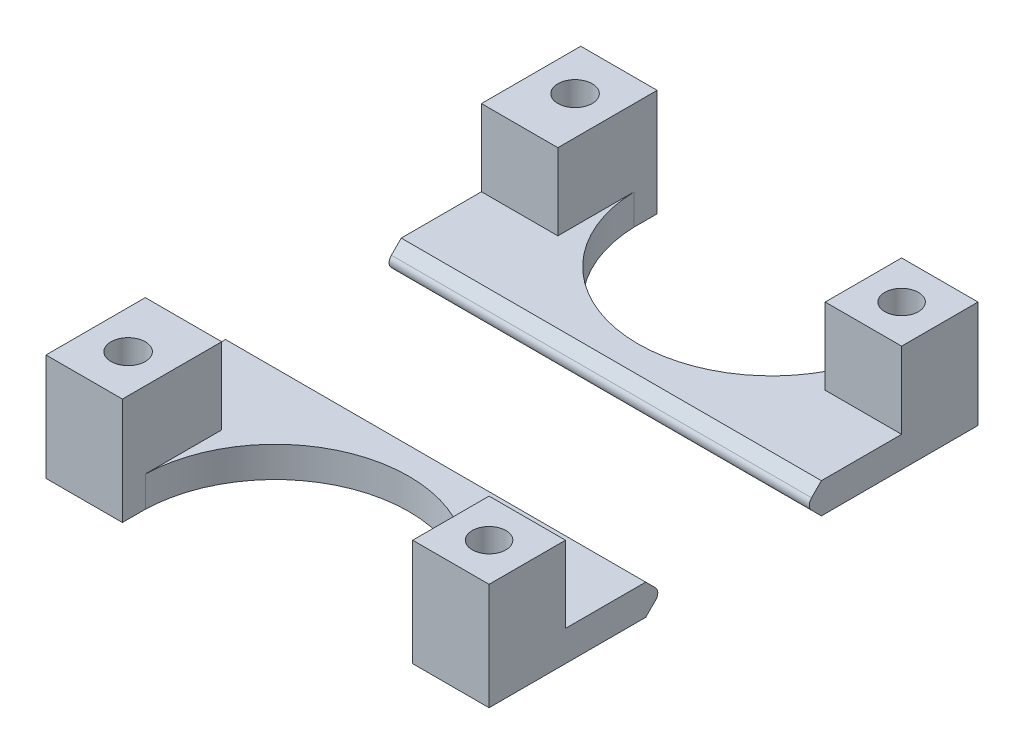
SolidWorks part; units mm, degrees
ref_plane "Front Plane" through (0, 0, 0) normal (0, 0, 1) x (1, 0, 0)
ref_plane "Top Plane" through (0, 0, 0) normal (0, 1, 0) x (1, 0, 0)
ref_plane "Right Plane" through (0, 0, 0) normal (1, 0, 0) x (0, 0, -1)
sketch "Sketch1" plane through (0, 0, 0) normal (0, 1, 0) x (1, 0, 0)
  line L0 (10, 10) -> (10, -10)
  line L2 (0, -20) -> (0, 20)
  line L4 (55, -20) -> (55, 20) construction
  line L5 (10, -10) -> (45, -10)
  line L6 (45, -10) -> (45, 10) construction
  line L7 (45, 10) -> (10, 10)
  line L8 (45, 10) -> (55, 10)
  line L11 (55, 10) -> (55, 20)
  line L13 (27.5, -20) -> (27.5, -10) construction
  line L14 (27.5, 10) -> (27.5, 20) construction
  line L16 (45, -10) -> (55, -10)
  line L17 (55, -20) -> (55, -10)
  line L18 (55, -20) -> (55, -32)
  line L19 (55, -32) -> (45, -32)
  line L20 (0, -32) -> (0, -35)
  line L21 (55, 20) -> (55, 32)
  line L22 (55, 32) -> (45, 32)
  line L23 (0, -35) -> (10, -35)
  line L24 (0, -20) -> (0, -32)
  line L26 (10, -35) -> (10, -32)
  line L27 (0, 20) -> (0, 32)
  line L29 (10, 32) -> (10, 35)
  line L30 (-55, 0) -> (55, 0) construction
  line L31 (0, 0) -> (55, 0) construction
  line L35 (10, 35) -> (0, 35)
  line L36 (0, 35) -> (0, 32)
  arc A26 (45, -32) -> (10, -32) centre (27.5, -32.5074) ccw
  arc A27 (45, 32) -> (10, 32) centre (27.5, 32.5074) cw
  circle A46 centre (50, 27) radius 2.2
  circle A47 centre (50, -27) radius 2.2
  circle A50 centre (5, 29.25) radius 2.2479
  circle A52 centre (5, -29.25) radius 2.2479
  point P30 (27.5, -15)
  point P35 (27.5, 15)
  point P36 (27.5, -10)
  point P39 (0, 0)
  dimension "D18" = 4.4
  dimension "D1" = 40
  dimension "D2" = 55
  dimension "D24" = 10
  dimension "D13" = 5
  dimension "D16" = 5
  dimension "D7" = 10
  dimension "D9" = 5
  dimension "D14" = 5
  dimension "D4" = 20
  dimension "D5" = 10
  dimension "D3" = 10
  dimension "D6" = 35
  dimension "D8" = 12
  dimension "D10" = 10
extrude "Extrude-Body" add sketch "Sketch1" along normal blind 4 contours L4 L2 A47 A46 L7 L6 L5 L0 | L19 L18 A47 | L22 L21 A46 | L27 | L24 region at (9.1098, 0, 0)
sketch "Sketch5" plane through (0, 4, 0) normal (0, 1, 0) x (1, 0, 0)
  line L9 (45, -22) -> (55, -22)
  line L21 (55, -22) -> (55, -32)
  line L23 (0, -35) -> (0, 35) construction
  line L36 (55, -32) -> (45, -32)
  line L37 (45, -32) -> (45, -22)
  line L38 (55, 22) -> (55, 32)
  line L39 (55, 32) -> (45, 32)
  line L41 (45, 32) -> (45, 22)
  line L42 (45, 22) -> (55, 22)
  line L43 (10, 22) -> (10, 35)
  line L45 (10, 35) -> (0, 35)
  line L46 (0, 35) -> (0, 22)
  line L47 (0, -35) -> (0, 35) construction
  line L48 (0, 22) -> (10, 22)
  line L49 (10, -22) -> (0, -22)
  line L50 (0, -22) -> (0, -35)
  line L52 (10, -35) -> (10, -22)
  line L55 (10, -35) -> (0, -35)
  circle A0 centre (50, 27) radius 2.2
  circle A3 centre (50, -27) radius 2.2
  circle A11 centre (50, 27) radius 2.2 construction
  circle A12 centre (50, -27) radius 2.2 construction
  circle A13 centre (5, -29.25) radius 2.2479 construction
  circle A14 centre (5, -29.25) radius 2.2479
  circle A15 centre (5, 29.25) radius 2.2479 construction
  circle A16 centre (5, 29.25) radius 2.2479
  dimension "D1" = 10
  dimension "D2" = 10
  dimension "D3" = 10
  dimension "D4" = 10
  dimension "D5" = 10
  dimension "D6" = 10
  dimension "D8" = 13
extrude "Extrude-Legs" add sketch "Sketch5" along normal blind 10
sketch "Sketch6" plane through (0, 4, 0) normal (0, 1, 0) x (1, 0, 0)
  line L0 (55, -10) -> (55, -22) construction
  line L1 (10, -10) -> (55, -10)
  line L2 (10, -10) -> (10, -9.5)
  line L3 (10, -9.5) -> (55, -9.5)
  line L4 (55, -10) -> (55, -9.5)
  line L5 (10, 10) -> (55, 10)
  line L6 (10, 10) -> (10, 9.5)
  line L7 (10, 9.5) -> (55, 9.5)
  line L8 (55, 10) -> (55, 9.5)
  line L9 (55, 10) -> (55, 22) construction
  dimension "D1" = 19
extrude "Boss-Extrude1" add sketch "Sketch6" against normal up to surface (4 mm away) up to face at (5, 0, 31.4979)
sketch "Sketch7" plane through (55, 0, 0) normal (1, 0, 0) x (0, 0, -1)
  line L0 (-10.2071, 2.7071) -> (-11.5, 4)
  line L1 (-9.5, 0) -> (-9.5, 4) construction
  line L2 (-9.5, 4) -> (-22, 4) construction
  line L3 (-10.2071, 1.2929) -> (-11.5, 0)
  line L4 (-9.5, 0) -> (-32, 0) construction
  line L5 (10.2071, 2.7071) -> (11.5, 4)
  line L6 (9.5, 0) -> (9.5, 4) construction
  line L7 (9.5, 4) -> (22, 4) construction
  line L8 (10.2071, 1.2929) -> (11.5, 0)
  line L9 (9.5, 0) -> (32, 0) construction
  line L10 (11.5, 4) -> (9.5, 4)
  line L11 (9.5, 0) -> (9.5, 4) construction
  line L12 (9.5, 4) -> (9.5, 0)
  line L13 (9.5, 0) -> (11.5, 0)
  line L14 (-11.5, 4) -> (-9.5, 4)
  line L15 (-9.5, 4) -> (-9.5, 0)
  line L16 (-9.5, 0) -> (-11.5, 0)
  line L17 (0, 0) -> (0, 8.2974) construction
  arc A0 (10.2071, 2.7071) -> (10.2071, 1.2929) centre (10.9142, 2) ccw
  arc A1 (-10.2071, 2.7071) -> (-10.2071, 1.2929) centre (-10.9142, 2) cw
  point P36 (9.5, 2)
  point P39 (-9.5, 2)
  dimension "D3" = 1
  dimension "D1" = 45
  dimension "D2" = 45
extrude "Cut-Extrude1" cut sketch "Sketch7" against normal up to surface (55 mm away) up to face at (0, 8, 0)
sketch "Sketch8" plane through (0, 4, 0) normal (0, 1, 0) x (1, 0, 0)
  line L0 (10, 9.5) -> (10, -9.5) construction
  line L1 (0, -9.5) -> (10, -9.5)
  line L2 (0, -9.5) -> (0, 9.5)
  line L3 (0, 9.5) -> (10, 9.5)
  line L4 (10, -9.5) -> (10, 9.5)
extrude "Cut-Extrude2" cut sketch "Sketch8" against normal blind 10
equation "\"boltdiameter\"=4.4"
equation "\"D18@Sketch1\"=\"boltdiameter\""
equation "\"boltfacediameter\"=7"
equation "\"insetNutFlat\"=8.4"
equation "\"screwInset\"=8.43"
equation "\"slotLength\"=80"
